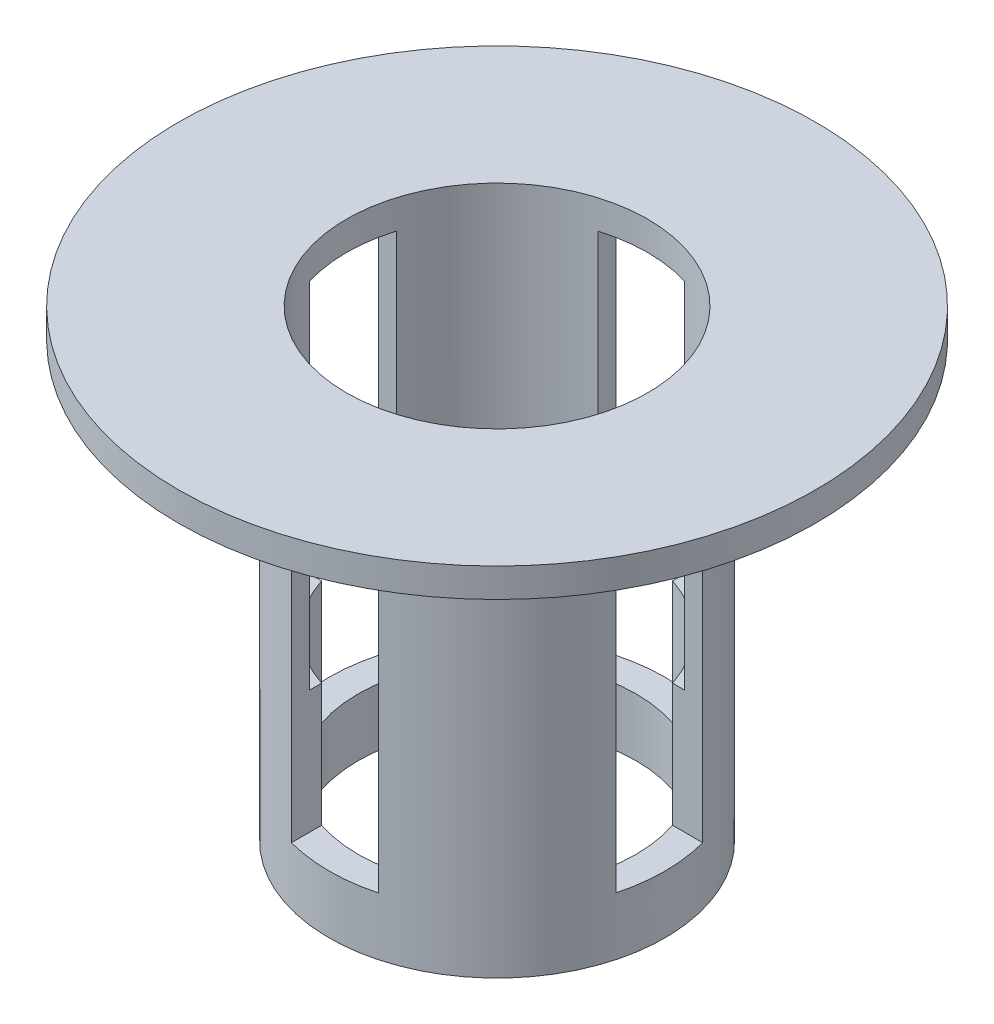
SolidWorks part; units mm, degrees
ref_plane "Front Plane" through (0, 0, 0) normal (0, 0, 1) x (1, 0, 0)
ref_plane "Top Plane" through (0, 0, 0) normal (0, 1, 0) x (1, 0, 0)
ref_plane "Right Plane" through (0, 0, 0) normal (1, 0, 0) x (0, 0, -1)
sketch "Sketch1" plane through (0, 0, 0) normal (0, 1, 0) x (1, 0, 0)
  circle A0 centre (0, 0) radius 6.604
  circle A1 centre (0, 0) radius 13.97
  dimension "D1" = 13.208
  dimension "D2" = 27.94
extrude "Stabilizer" add sketch "Sketch1" along normal blind 1.27
sketch "Sketch2" plane through (0, 0, 0) normal (0, -1, 0) x (-1, 0, 0)
  circle A0 centre (0, 0) radius 6.604
  circle A1 centre (0, 0) radius 7.366
  circle A2 centre (0, 0) radius 6.604 construction
  dimension "D1" = 14.732
extrude "Large End" add sketch "Sketch2" along normal blind 11.1125 contours A1 | A0
sketch "Sketch3" plane through (0, -11.1125, 0) normal (0, -1, 0) x (-1, 0, 0)
  circle A0 centre (0, 0) radius 6.096
  circle A1 centre (0, 0) radius 7.366
  circle A2 centre (0, 0) radius 7.366 construction
  dimension "D1" = 12.192
extrude "Small End" add sketch "Sketch3" along normal blind 7.9375
sketch "Sketch4" plane through (0, -19.05, 0) normal (0, -1, 0) x (-1, 0, 0)
  circle A0 centre (0, 0) radius 7.366 construction
  point P0 (0, -7.366)
ref_plane "Plane1" through (0, -19.05, 7.366) normal (0, 0, 1) x (1, 0, 0)
sketch "Sketch5" plane through (0, -19.05, 7.366) normal (0, 0, 1) x (1, 0, 0)
  line L1 (1.905, 2.54) -> (-1.905, 2.54)
  line L2 (1.905, 2.54) -> (1.905, 19.05)
  line L3 (1.905, 19.05) -> (-1.905, 19.05)
  line L4 (-1.905, 2.54) -> (-1.905, 19.05)
  line L5 (-7.366, 0) -> (7.366, 0) construction
  line L6 (-7.366, 19.05) -> (7.366, 19.05) construction
  dimension "D1" = 3.81
  dimension "D2" = 2.54
extrude "Cut-Extrude1" cut sketch "Sketch5" against normal through all
sketch "Sketch6" plane through (0, -19.05, 0) normal (0, -1, 0) x (-1, 0, 0)
  circle A0 centre (0, 0) radius 7.366 construction
  point P0 (-7.366, 0)
ref_plane "Plane2" through (7.366, -19.05, 0) normal (1, 0, 0) x (0, 0, -1)
sketch "Sketch7" plane through (7.366, -19.05, 0) normal (1, 0, 0) x (0, 0, -1)
  line L0 (-7.366, 0) -> (7.366, 0) construction
  line L1 (1.905, 2.54) -> (-1.905, 2.54)
  line L2 (1.905, 2.54) -> (1.905, 19.05)
  line L3 (1.905, 19.05) -> (-1.905, 19.05)
  line L4 (-1.905, 2.54) -> (-1.905, 19.05)
  line L5 (-7.1154, 19.05) -> (7.1154, 19.05) construction
  line L6 (0, 2.54) -> (0, 0) construction
  dimension "D1" = 3.81
  dimension "D2" = 2.54
extrude "Cut-Extrude2" cut sketch "Sketch7" against normal through all contours L2 L3 L4 L1
